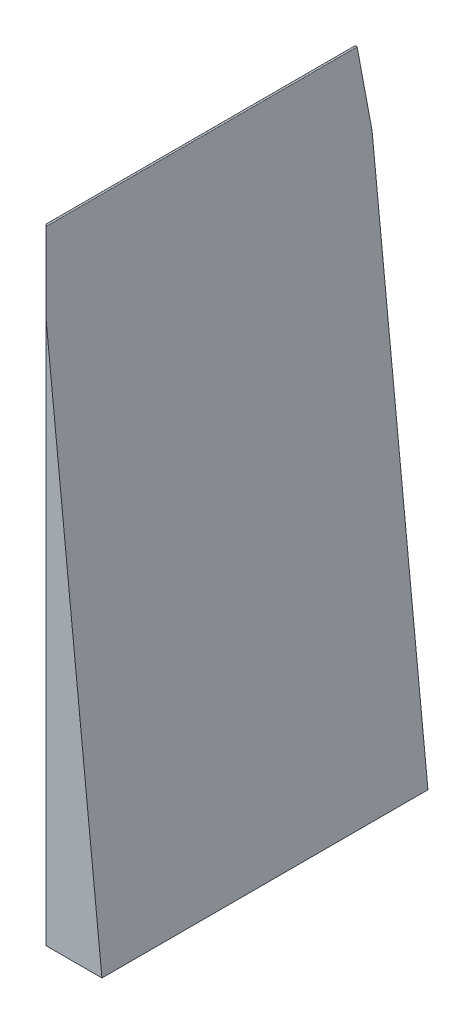
SolidWorks part; units mm, degrees
ref_plane "Front Plane" through (0, 0, 0) normal (0, 0, 1) x (1, 0, 0)
ref_plane "Top Plane" through (0, 0, 0) normal (0, 1, 0) x (1, 0, 0)
ref_plane "Right Plane" through (0, 0, 0) normal (1, 0, 0) x (0, 0, -1)
sketch "Sketch1" plane through (0, 0, 0) normal (0, 0, 1) x (1, 0, 0)
  line L0 (0, 0) -> (0, 86.36)
  line L1 (0, 86.36) -> (8.89, 0)
  line L2 (8.89, 0) -> (0, 0)
  dimension "D1" = 8.89
  dimension "D2" = 86.36
extrude "Boss-Extrude1" add sketch "Sketch1" along normal blind 44.45
fillet "Fillet1" radius 0.127 1 edges at (0, 86.36, 22.225)
chamfer "Chamfer1" [suppressed] distance 1.27 angle 45 tangent propagation no
chamfer "Chamfer2" distance 1.27 angle 45 3 edges at (0, 41.943, 0) (0, 0, 22.225) (0, 41.943, 44.45) tangent propagation no
